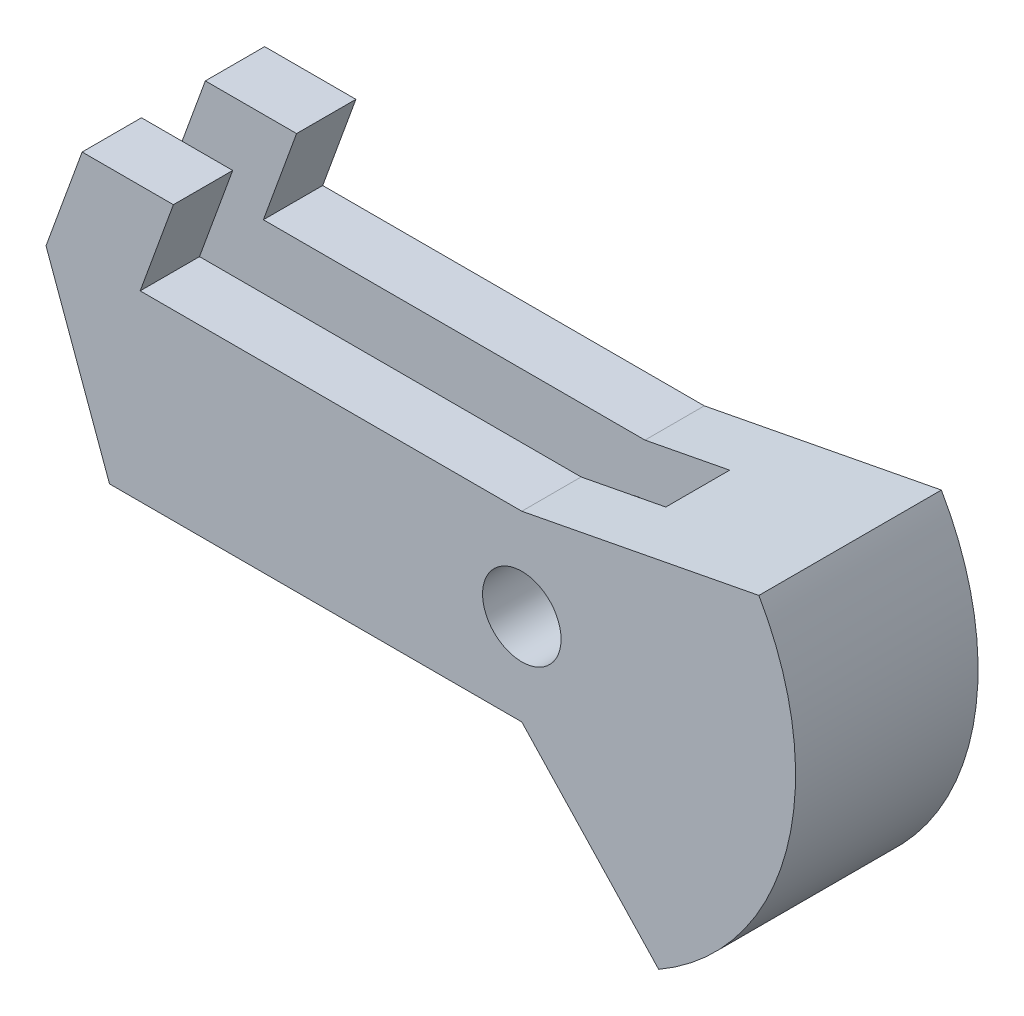
SolidWorks part; units mm, degrees
ref_plane "Front Plane" through (0, 0, 0) normal (0, 0, 1) x (1, 0, 0)
ref_plane "Top Plane" through (0, 0, 0) normal (0, 1, 0) x (1, 0, 0)
ref_plane "Right Plane" through (0, 0, 0) normal (1, 0, 0) x (0, 0, -1)
sketch "Sketch5" plane through (0, 0, 0) normal (0, 0, 1) x (1, 0, 0)
  line L0 (0, 0) -> (12.9904, 7.5) construction
  line L1 (0, 0) -> (7.5, -12.9904) construction
  line L2 (0, 0) -> (15, 0) construction
  line L3 (12.9904, 7.5) -> (0, 5)
  line L4 (0, 5) -> (-20.9099, 5)
  line L5 (0, -5) -> (7.5, -12.9904)
  line L6 (0, -5) -> (-22.5911, -5)
  line L7 (-20.9099, 5) -> (-19.0901, 10)
  line L9 (-19.0901, 10) -> (-24.0901, 10)
  line L10 (-24.0901, 10) -> (-26.0704, 4.5592)
  line L11 (-20, 7.5) -> (-20, 1.3012) construction
  line L12 (-26.0704, 4.5592) -> (-22.5911, -5)
  arc A0 (7.5, -12.9904) -> (12.9904, 7.5) centre (0, 0) ccw
  circle A1 centre (0, 0) radius 5 construction
  point P14 (-20, 7.5)
  point P17 (-25.9088, 5)
  dimension "D3" = 10
  dimension "D4" = 15
  dimension "D1" = 30
  dimension "D2" = 60
  dimension "D5" = 70
  dimension "D6" = 5
  dimension "D7" = 5
  dimension "D8" = 20
  dimension "D9" = 70
  dimension "D10" = 5
extrude "Boss-Extrude2" add sketch "Sketch5" along normal mid plane 10
sketch "Sketch6" plane through (0, 0, 0) normal (0, 0, 1) x (1, 0, 0)
  line L0 (-19.0901, 10) -> (-20.9099, 5)
  line L1 (-19.0901, 10) -> (-20.9099, 5)
  line L2 (-20.9099, 5) -> (0, 5)
  line L3 (-20.9099, 5) -> (0, 5)
  line L4 (0, 5) -> (12.9904, 7.5)
  line L5 (0, 5) -> (4.6394, 5.8929)
  line L6 (7.5, -12.9904) -> (0, -5)
  line L7 (2.0725, -7.208) -> (0, -5)
  line L8 (0, -5) -> (-22.5911, -5)
  line L9 (0, -5) -> (-22.5911, -5)
  line L10 (-26.0704, 4.5592) -> (-24.0901, 10)
  line L11 (-26.0704, 4.5592) -> (-24.0901, 10)
  line L12 (-24.0901, 10) -> (-19.0901, 10)
  line L13 (-24.0901, 10) -> (-19.0901, 10)
  line L14 (-22.5911, -5) -> (-26.0704, 4.5592)
  line L19 (-22.5911, -5) -> (-26.0704, 4.5592)
  arc A0 (7.5, -12.9904) -> (12.9904, 7.5) centre (0, 0) ccw
  arc A2 (2.0725, -7.208) -> (4.6394, 5.8929) centre (0, 0) ccw
  dimension "D1" = 7.5
extrude "Cut-Extrude1" cut sketch "Sketch6" against normal mid plane 3.5
hole_wizard "M4 Clearance Hole1" positions "Sketch7" profile "Sketch8" hole size "M4" standard "ANSI Metric" end condition through all
sketch "Sketch7" plane through (0, 0, 5) normal (0, 0, 1) x (1, 0, 0)
  point P0 (0, 0)
sketch "Sketch8" plane through (0, 0, 5) normal (1, 0, 0) x (0, -1, 0)
  line L0 (0, 0) -> (0, 10)
  line L1 (0, 10) -> (2.15, 10)
  line L2 (2.15, 10) -> (2.15, 0)
  line L5 (2.15, 0) -> (0, 0)
  line L11 (0, -6.35) -> (0, 107.95) construction
  dimension "Thru Hole Dia." = 4.3
  dimension "Thru Hole Depth" = 10
